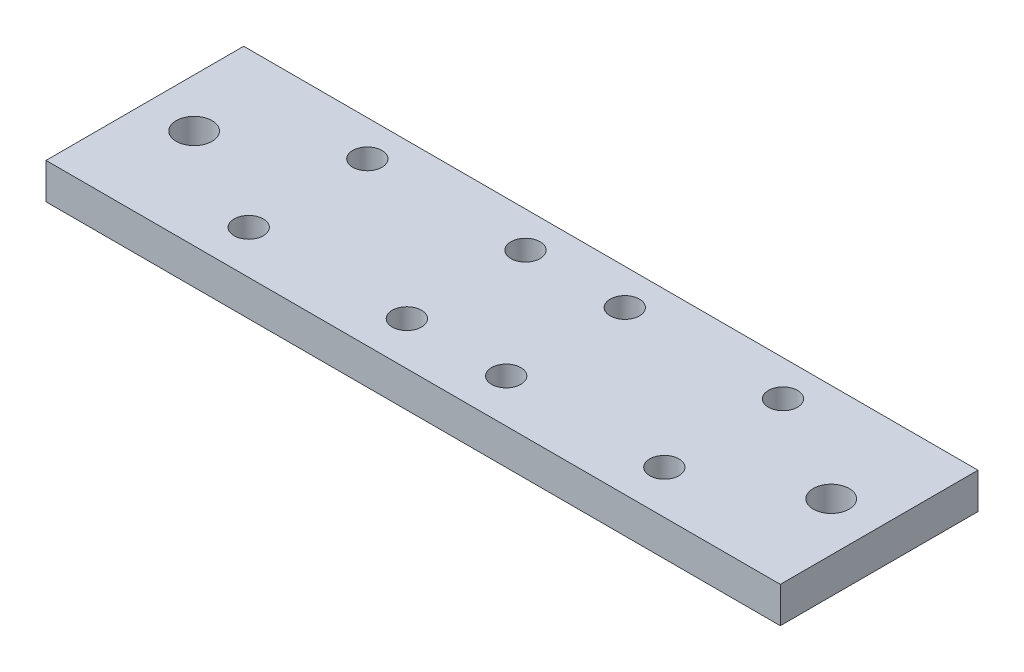
SolidWorks part; units mm, degrees
material "Alumina"
ref_plane "Front Plane" through (0, 0, 0) normal (0, 0, 1) x (1, 0, 0)
ref_plane "Top Plane" through (0, 0, 0) normal (0, 1, 0) x (1, 0, 0)
ref_plane "Right Plane" through (0, 0, 0) normal (1, 0, 0) x (0, 0, -1)
sketch "Sketch1" plane through (0, 0, 0) normal (0, 1, 0) x (1, 0, 0)
  line L1 (0, 0) -> (130, 0)
  line L2 (0, 0) -> (0, -35)
  line L3 (0, -35) -> (130, -35)
  line L4 (130, 0) -> (130, -35)
  dimension "D1" = 130
  dimension "D2" = 35
extrude "Boss-Extrude1" add sketch "Sketch1" along normal blind 6.35
sketch "Sketch5" plane through (0, 6.35, 0) normal (0, 1, 0) x (1, 0, 0)
  line L1 (0, 0) -> (0, -35) construction
  line L2 (130, -35) -> (130, 0) construction
  circle A0 centre (8.605, -17.3826) radius 3.18
  circle A2 centre (121.395, -17.3826) radius 3.18
  dimension "D1" = 8.605
  dimension "D2" = 8.605
extrude "Cut-Extrude2" cut sketch "Sketch5" against normal through all
sketch "Sketch8" plane through (0, 0, 0) normal (0, -1, 0) x (1, 0, 0)
  circle A16 centre (28.2089, 6.3204) radius 2.5866 construction
  circle A17 centre (28.2089, 27.3204) radius 2.5866 construction
  circle A18 centre (56.2089, 27.3204) radius 2.5866 construction
  circle A19 centre (56.2089, 6.3204) radius 2.5866 construction
  circle A20 centre (73.7909, 6.3204) radius 2.5866 construction
  circle A21 centre (73.7909, 27.3204) radius 2.5866 construction
  circle A22 centre (101.7909, 6.3204) radius 2.5866 construction
  circle A23 centre (101.7909, 27.3204) radius 2.5866 construction
  circle A24 centre (28.2089, 6.3204) radius 2.5866
  circle A25 centre (28.2089, 27.3204) radius 2.5866
  circle A26 centre (56.2089, 27.3204) radius 2.5866
  circle A27 centre (56.2089, 6.3204) radius 2.5866
  circle A28 centre (73.7909, 6.3204) radius 2.5866
  circle A29 centre (73.7909, 27.3204) radius 2.5866
  circle A30 centre (101.7909, 6.3204) radius 2.5866
  circle A31 centre (101.7909, 27.3204) radius 2.5866
extrude "Cut-Extrude4" cut sketch "Sketch8" against normal through all
